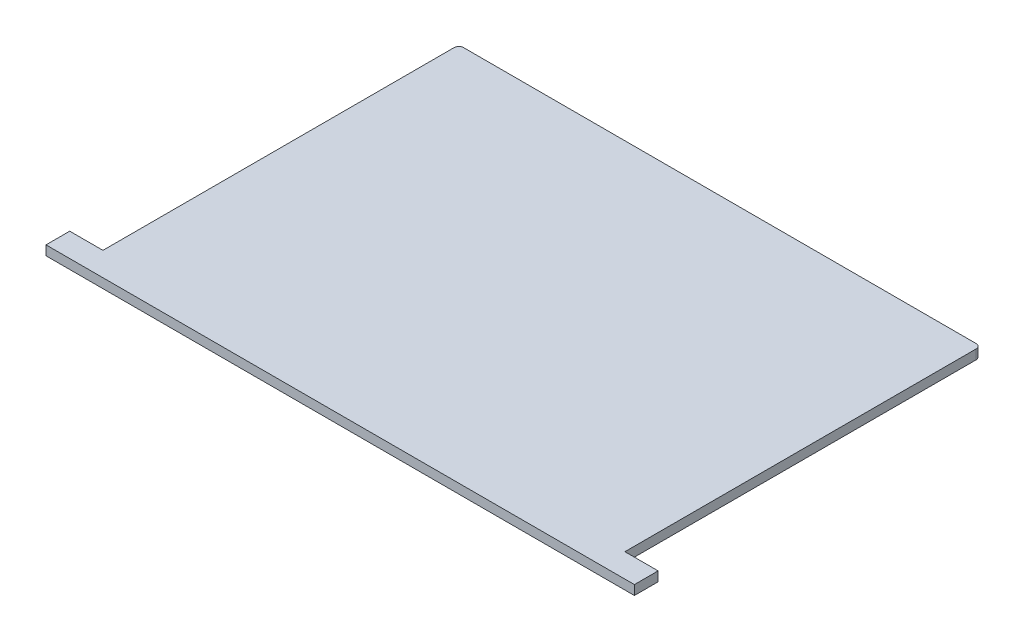
SolidWorks part; units mm, degrees
material "ABS"
ref_plane "Front Plane" through (0, 0, 0) normal (0, 0, 1) x (1, 0, 0)
ref_plane "Top Plane" through (0, 0, 0) normal (0, 1, 0) x (1, 0, 0)
ref_plane "Right Plane" through (0, 0, 0) normal (1, 0, 0) x (0, 0, -1)
sketch "Sketch1" plane through (0, 0, 0) normal (0, 1, 0) x (1, 0, 0)
  line L1 (-27.5, -20) -> (27.5, -20)
  line L3 (-27.5, 20) -> (27.5, 20)
  line L5 (-27.5, -20) -> (27.5, 20) construction
  line L6 (-27.5, 20) -> (27.5, -20) construction
  line L17 (-27.5, 20) -> (-27.5, -17.5)
  line L18 (-31, -17.5) -> (-31, -20)
  line L19 (-31, -20) -> (-27.5, -20)
  line L20 (-27.5, -17.5) -> (-31, -17.5)
  line L21 (27.5, 20) -> (27.5, -17.5)
  line L22 (27.5, -17.5) -> (31, -17.5)
  line L23 (31, -17.5) -> (31, -20)
  line L24 (31, -20) -> (27.5, -20)
  point P0 (0, 0)
  dimension "D1" = 2.5
  dimension "D2" = 3.5
  dimension "D3" = 55
  dimension "D4" = 40
  dimension "D5" = 3.5
  dimension "D6" = 2.5
extrude "Boss-Extrude1" add sketch "Sketch1" along normal blind 1
fillet "Fillet1" radius 0.5 2 edges at (27.5, 0.5, -20) (-27.5, 0.5, -20)
